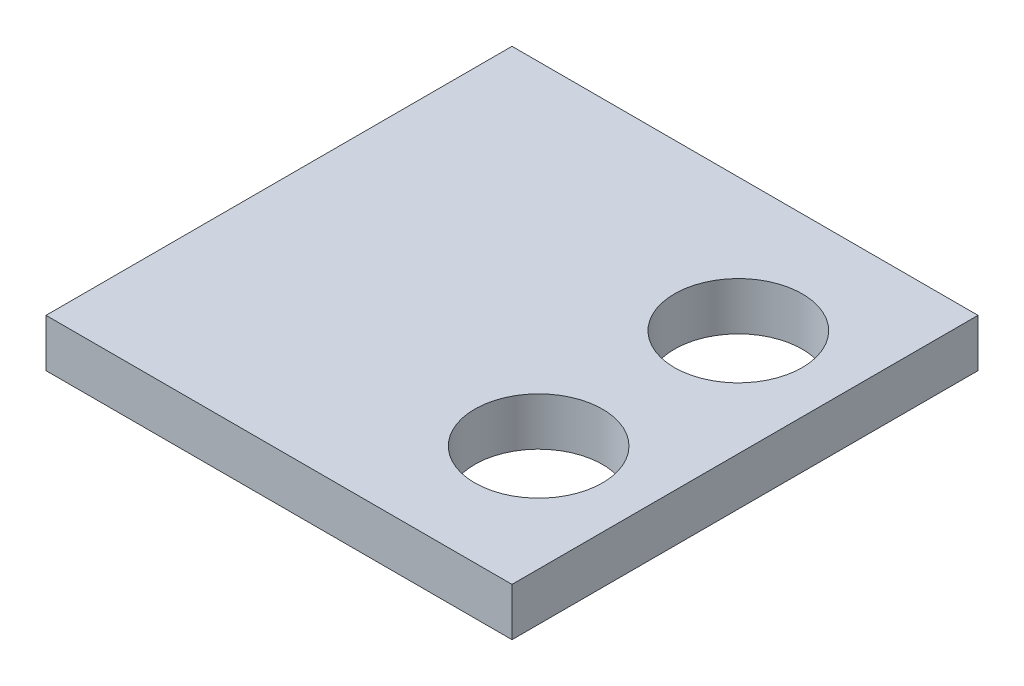
SolidWorks part; units mm, degrees
ref_plane "Front Plane" through (0, 0, 0) normal (0, 0, 1) x (1, 0, 0)
ref_plane "Top Plane" through (0, 0, 0) normal (0, 1, 0) x (1, 0, 0)
ref_plane "Right Plane" through (0, 0, 0) normal (1, 0, 0) x (0, 0, -1)
sketch "Sketch1" plane through (0, 0, 0) normal (0, 1, 0) x (1, 0, 0)
  line L1 (0, 0) -> (8.89, 0)
  line L2 (0, 0) -> (0, 8.89)
  line L3 (0, 8.89) -> (8.89, 8.89)
  line L4 (8.89, 0) -> (8.89, 8.89)
  dimension "D1" = 8.89
  dimension "D2" = 8.89
base flange "Base-Flange1" sketch "Sketch1" thickness 0.9144 reverse thickness direction no parameters "D1"=0.762
hole_wizard "#2 Clearance Hole1" positions "Sketch6" profile "Sketch7" hole size "#2" standard "ANSI Inch" end condition through all
sketch "Sketch6" plane through (0, 0, 0) normal (0, 1, 0) x (1, 0, 0)
  line L0 (0, 0) -> (8.89, 0) construction
  line L1 (8.89, 0) -> (8.89, 8.89) construction
  point P0 (6.858, 2.54)
  point P2 (6.858, 6.35)
  dimension "D1" = 3.81
  dimension "D2" = 2.54
  dimension "D3" = 2.032
sketch "Sketch7" plane through (6.858, 0, -2.54) normal (1, 0, 0) x (0, 0, 1)
  line L0 (0, 0) -> (0, 0.9144)
  line L1 (0, 0.9144) -> (1.2192, 0.9144)
  line L2 (1.2192, 0.9144) -> (1.2192, 0)
  line L5 (1.2192, 0) -> (0, 0)
  line L11 (0, -6.35) -> (0, 107.95) construction
  dimension "Thru Hole Dia." = 2.4384
  dimension "Thru Hole Depth" = 0.9144
sketch "Bend-Lines1" [suppressed] plane through (0, 0, 0) normal (0, 1, 0) x (1, 0, 0)
sketch "Bounding-Box1" [suppressed] plane through (0, 0, 0) normal (0, 1, 0) x (1, 0, 0)
sheet metal parameters "Sheet-Metal1" thickness 0.9144 parameters "D1"=0.762
flat pattern "Flat-Pattern1" [suppressed]
sketch "Bend-Lines2" plane through (0, 0, 0) normal (0, 1, 0) x (1, 0, 0)
sketch3d "Bounding-Box2" [suppressed]
  line L0 (0, 0, 0) -> (0, 8.89, 0) construction
  line L1 (-8.89, 0, 0) -> (-8.89, 8.89, 0) construction
  line L2 (0, 0, 0) -> (-8.89, 0, 0) construction
  line L3 (0, 8.89, 0) -> (-8.89, 8.89, 0) construction
sheet metal parameters "Sheet-Metal2" thickness 0.9144 parameters "D1"=0.762
flat pattern "Flat-Pattern1"
sketch "Bend-Lines2" plane through (0, 0, 0) normal (0, 1, 0) x (1, 0, 0)
sketch3d "Bounding-Box2" [suppressed]
  line L0 (0, 0, 0) -> (0, 8.89, 0) construction
  line L1 (8.89, 0, 0) -> (8.89, 8.89, 0) construction
  line L2 (0, 0, 0) -> (8.89, 0, 0) construction
  line L3 (0, 8.89, 0) -> (8.89, 8.89, 0) construction
